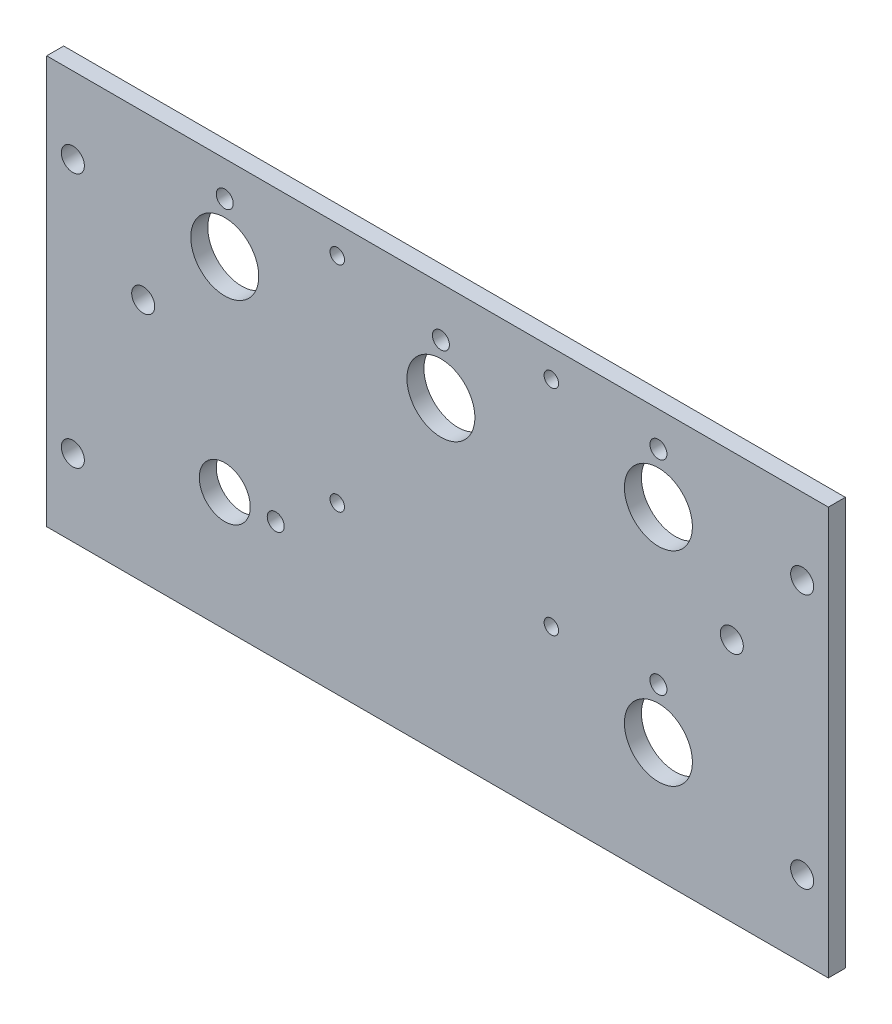
SolidWorks part; units mm, degrees
ref_plane "Front Plane" through (0, 0, 0) normal (0, 0, 1) x (1, 0, 0)
ref_plane "Top Plane" through (0, 0, 0) normal (0, 1, 0) x (1, 0, 0)
ref_plane "Right Plane" through (0, 0, 0) normal (1, 0, 0) x (0, 0, -1)
sketch "Sketch1" plane through (0, 0, 0) normal (0, 0, 1) x (1, 0, 0)
  line L4 (0, 76.2) -> (-146.05, 76.2)
  line L5 (-146.05, 76.2) -> (-146.05, 0)
  line L6 (-146.05, 0) -> (0, 0)
  line L7 (0, 0) -> (0, 76.2)
  line L8 (0, 76.2) -> (-146.05, 76.2)
  line L9 (-146.05, 76.2) -> (-146.05, 0)
  line L10 (-146.05, 0) -> (0, 0)
  line L11 (0, 0) -> (0, 76.2)
  dimension "D1" = 0
extrude "Boss-Extrude1" add sketch "Sketch1" against normal blind 3.175
hole_wizard "#6 Clearance Hole1" positions "Sketch3" profile "Sketch2" hole size "#6" standard "ANSI Inch" end condition through all
sketch "Sketch3" plane through (0, 0, -3.175) normal (0, 0, -1) x (-1, 0, 0)
  point P0 (4.8895, 61.9125)
  point P3 (4.8895, 14.2875)
  point P6 (141.1605, 14.2875)
  point P9 (141.1605, 61.9125)
  point P12 (128.016, 45.72)
  point P15 (18.034, 45.72)
sketch "Sketch2" plane through (-4.8895, 61.9125, -3.175) normal (1, 0, 0) x (0, 1, 0)
  line L0 (0, 0) -> (0, 3.175)
  line L1 (0, 3.175) -> (2.1526, 3.175)
  line L2 (2.1526, 3.175) -> (2.1526, 0)
  line L5 (2.1526, 0) -> (0, 0)
  line L11 (0, -6.35) -> (0, 107.95) construction
  dimension "Thru Hole Dia." = 4.3053
  dimension "Thru Hole Depth" = 3.175
hole_wizard "3/8 (0.375) Diameter Hole1" positions "Sketch7" profile "Sketch6" hole size "3/8" standard "ANSI Inch" end condition through all
sketch "Sketch7" plane through (0, 0, -3.175) normal (0, 0, -1) x (-1, 0, 0)
  line L0 (0, 0) -> (0, 76.2) construction
  line L1 (0, 76.2) -> (146.05, 76.2) construction
  point P3 (112.776, 22.225)
  dimension "D1" = 112.776
  dimension "D2" = 53.975
sketch "Sketch6" plane through (-112.776, 22.225, -3.175) normal (1, 0, 0) x (0, 1, 0)
  line L0 (0, 0) -> (0, 3.175)
  line L1 (0, 3.175) -> (4.7625, 3.175)
  line L2 (4.7625, 3.175) -> (4.7625, 0)
  line L5 (4.7625, 0) -> (0, 0)
  line L11 (0, -6.35) -> (0, 107.95) construction
  dimension "Thru Hole Dia." = 9.525
  dimension "Thru Hole Depth" = 3.175
hole_wizard "1/2 (0.5) Diameter Hole1" positions "Sketch5" profile "Sketch4" hole size "1/2" standard "ANSI Inch" end condition through all
sketch "Sketch5" plane through (0, 0, -3.175) normal (0, 0, -1) x (-1, 0, 0)
  line L0 (0, 0) -> (0, 76.2) construction
  line L1 (0, 76.2) -> (146.05, 76.2) construction
  line L2 (0, 38.1) -> (146.05, 38.1) construction
  line L3 (146.05, 76.2) -> (146.05, 0) construction
  line L5 (112.776, 22.225) -> (31.75, 22.225) construction
  point P0 (31.75, 60.325)
  point P3 (72.39, 57.658)
  point P6 (112.776, 60.325)
  point P29 (31.75, 22.225)
  dimension "D1" = 31.75
  dimension "D2" = 15.875
  dimension "D3" = 2.667
  dimension "D4" = 40.64
  dimension "D5" = 81.026
sketch "Sketch4" plane through (-31.75, 60.325, -3.175) normal (1, 0, 0) x (0, 1, 0)
  line L0 (0, 0) -> (0, 3.175)
  line L1 (0, 3.175) -> (6.35, 3.175)
  line L2 (6.35, 3.175) -> (6.35, 0)
  line L5 (6.35, 0) -> (0, 0)
  line L11 (0, -6.35) -> (0, 107.95) construction
  dimension "Thru Hole Dia." = 12.7
  dimension "Thru Hole Depth" = 3.175
hole_wizard "1/8 (0.125) Diameter Hole1" positions "Sketch9" profile "Sketch8" hole size "1/8" standard "ANSI Inch" end condition through all
sketch "Sketch9" plane through (0, 0, -3.175) normal (0, 0, -1) x (-1, 0, 0)
  line L0 (31.75, 69.6995) -> (31.75, 60.325) construction
  line L2 (72.39, 57.658) -> (72.39, 67.0325) construction
  line L4 (112.776, 60.325) -> (112.776, 69.6995) construction
  line L6 (31.75, 22.225) -> (31.75, 31.5995) construction
  line L8 (72.39, 19.558) -> (72.39, 28.9325) construction
  point P0 (31.75, 69.6995)
  point P2 (112.776, 69.6995)
  point P4 (103.251, 22.225)
  point P14 (72.39, 67.0325)
  point P23 (31.75, 31.5995)
  dimension "D1" = 9.3745
sketch "Sketch8" plane through (-31.75, 69.6995, -3.175) normal (1, 0, 0) x (0, 1, 0)
  line L0 (0, 0) -> (0, 3.175)
  line L1 (0, 3.175) -> (1.5875, 3.175)
  line L2 (1.5875, 3.175) -> (1.5875, 0)
  line L5 (1.5875, 0) -> (0, 0)
  line L11 (0, -6.35) -> (0, 107.95) construction
  dimension "Thru Hole Dia." = 3.175
  dimension "Thru Hole Depth" = 3.175
hole_wizard "CSK for #2 Flat Head Machine Screw (100)1" positions "Sketch10" profile "Sketch11" countersink size "#2" standard "ANSI Inch" end condition through all
sketch "Sketch10" plane through (0, 0, -3.175) normal (0, 0, -1) x (-1, 0, 0)
  point P1 (51.753, 70.9951)
  point P3 (91.753, 70.9951)
  point P5 (91.753, 30.9951)
  point P7 (51.753, 30.9951)
sketch "Sketch11" plane through (-51.753, 70.9951, -3.175) normal (1, 0, 0) x (0, 1, 0)
  line L0 (0, 0) -> (0, 3.175)
  line L1 (0, 3.175) -> (1.3525, 3.175)
  line L2 (1.3525, 3.175) -> (1.3525, 0.698)
  line L3 (1.3525, 0.698) -> (2.1844, 0)
  line L5 (2.1844, 0) -> (0, 0)
  line L6 (-1.3525, 0.698) -> (-2.1844, 0) construction
  line L11 (0, -6.35) -> (0, 107.95) construction
  dimension "Thru Hole Dia." = 2.7051
  dimension "Thru Hole Depth" = 3.175
  dimension "Near C'Sink Dia." = 4.3688
  dimension "Near C'Sink Angle" = 100
